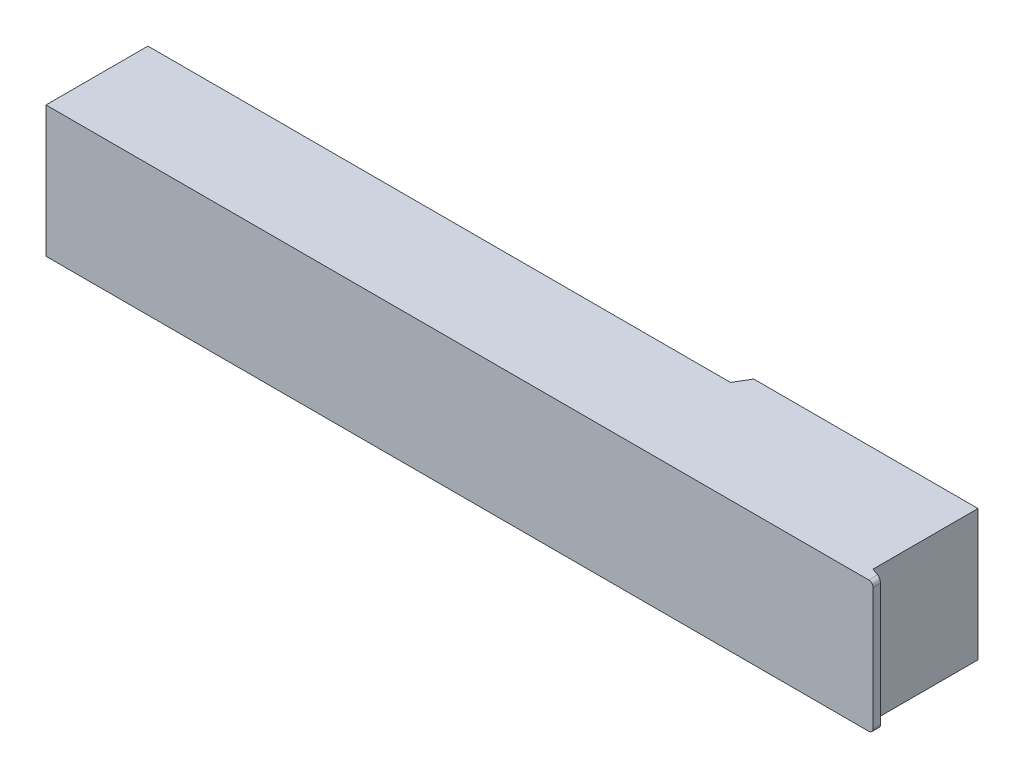
SolidWorks part; units mm, degrees
ref_plane "Front Plane" through (0, 0, 0) normal (1, 0, 0) x (0, 1, 0)
ref_plane "Top Plane" through (0, 0, 0) normal (0, 0, 1) x (0, 1, 0)
ref_plane "Right Plane" through (0, 0, 0) normal (0, 1, 0) x (-1, 0, 0)
sketch "Sketch1" plane through (0, 0, 0) normal (0, 0, 1) x (0, 1, 0)
  line L1 (0, 0) -> (22.5, 0)
  line L2 (0, 0) -> (0, -142)
  line L3 (0, -142) -> (22.5, -142)
  line L4 (22.5, 0) -> (22.5, -142)
extrude "Boss-Extrude1" add sketch "Sketch1" against normal blind 20 contours L2 L3 L4 L1
sketch "Sketch2" plane through (142, 0, 0) normal (1, 0, 0) x (0, 1, 0)
  line L0 (22.5, -20) -> (22.5, 0) construction
  line L1 (0, -20) -> (22.5, -20)
  line L2 (0, -20) -> (0, -2)
  line L3 (0, -2) -> (22.5, -2)
  line L4 (22.5, -20) -> (22.5, -2)
extrude "Cut-Extrude1" cut sketch "Sketch2" against normal blind 2 contours L3 L4 L1 L2
chamfer "Chamfer5" distance 0.75 angle 70 1 edges at (142, 11.25, -2) first distance on face at (142, 11.25, -1)
fillet "Fillet5" radius 0.75 2 edges at (142, 0, -0.625) (142, 22.5, -0.625)
sketch "Sketch3" plane through (0, 22.5, 0) normal (0, 1, 0) x (-1, 0, 0)
  line L0 (0, 0) -> (-141.25, 0) construction
  line L1 (-140, -20) -> (-30, -20)
  line L2 (-140, -20) -> (-140, 0)
  line L3 (-140, 0) -> (-30, 0)
  line L4 (-30, -20) -> (-30, 0)
  line L5 (0, -20) -> (0, 0) construction
  line L6 (-30, -20) -> (0, -20)
  line L7 (-30, -20) -> (-30, -10)
  line L8 (-30, -10) -> (0, -10)
  line L9 (0, -20) -> (0, -10)
  line L11 (-30, 0) -> (0, 0)
  line L12 (-30, 0) -> (-30, -2.5)
  line L17 (-30, -2.5) -> (0, -2.5)
  line L18 (0, 0) -> (0, -2.5)
extrude "Cut-Extrude2" [suppressed] cut sketch "Sketch3" against normal up to surface (22.5 mm away) contours L12 L17 L18 L11 up to face at (93.75, 0, -7.2502)
sketch3d "3DSketch1" plane through (0, 0, 0) normal (0, 0, 1) x (1, 0, 0)
  dimension "D1" = 11.25
sketch "Sketch4" plane through (0, 11.25, 0) normal (0, 1, 0) x (1, 0, 0)
  line L0 (30, 20) -> (165, 20)
  line L1 (140, 20) -> (30, 20) construction
  line L2 (165, 20) -> (165, 7.5)
  line L3 (165, 7.5) -> (30, 20)
  dimension "D1" = 12.5
  dimension "D2" = 135
sketch "Sketch5" plane through (0, 0, -20) normal (0, 0, -1) x (-1, 0, 0)
  line L0 (0, 22.5) -> (-140, 22.5) construction
  line L1 (-140, 0) -> (-91.5, 0)
  line L2 (-140, 0) -> (-140, 22.5)
  line L3 (-140, 22.5) -> (-91.5, 22.5)
  line L4 (-91.5, 0) -> (-91.5, 22.5)
  line L5 (-138, 2) -> (-93.5, 2)
  line L6 (-93.5, 2) -> (-93.5, 20.5)
  line L7 (-138, 20.5) -> (-93.5, 20.5)
  line L8 (-138, 2) -> (-138, 20.5)
  line L9 (-93.5, 20.5) -> (-91.5, 22.5)
  line L10 (-93.5, 2) -> (-91.5, 0)
  line L12 (-91.5, 22.5) -> (0, 22.5)
  line L13 (-91.5, 22.5) -> (-91.5, 0)
  line L14 (-91.5, 0) -> (0, 0)
  line L15 (0, 22.5) -> (0, 0)
  line M6 (-140, 0) -> (0, 0)
  line M7 (0, 0) -> (0, 22.5)
  line M8 (0, 22.5) -> (-140, 22.5)
  dimension "D1" = 2
extrude "Cut-Extrude3" [suppressed] cut sketch "Sketch5" against normal blind 7.5 contours L8 L5 L6 L7 | L6 L10 L4 L9 | L4 M6 M7 M8
sketch "Sketch6" plane through (0, 22.5, 0) normal (0, 1, 0) x (-1, 0, 0)
  line L0 (-100, -17.5) -> (-101.5, -20)
  line L1 (-140, -20) -> (-100, -20) construction
  line L2 (-140, -20) -> (-140, -17.5) construction
  line L3 (-140, -17.5) -> (-100, -17.5) construction
  line L4 (-100, -20) -> (-100, -17.5) construction
  line L6 (-100, -20) -> (-101.5, -20)
  line L7 (-100, -17.5) -> (0, -17.5)
  line L8 (-100, -17.5) -> (-100, -20) construction
  line L9 (-100, -20) -> (0, -20)
  line L10 (0, -17.5) -> (0, -20)
  point P5 (0, 0)
  point P7 (0, 0)
  dimension "D1" = 100
  dimension "D2" = 101.5
extrude "Cut-Extrude4" cut sketch "Sketch6" against normal through all and the other way through all
equation "\"whitekey_cutout_length\"= 101.5"
equation "\"mount_recess_length\"=50"
equation "\"mount_recess_height\"=12.5"
equation "\"mount_recess_depth\"=1.5"
equation "\"D1@Sketch6\"=\"whitekey_cutout_length\"-1.5"
equation "\"D2@Sketch6\"=\"whitekey_cutout_length\""
